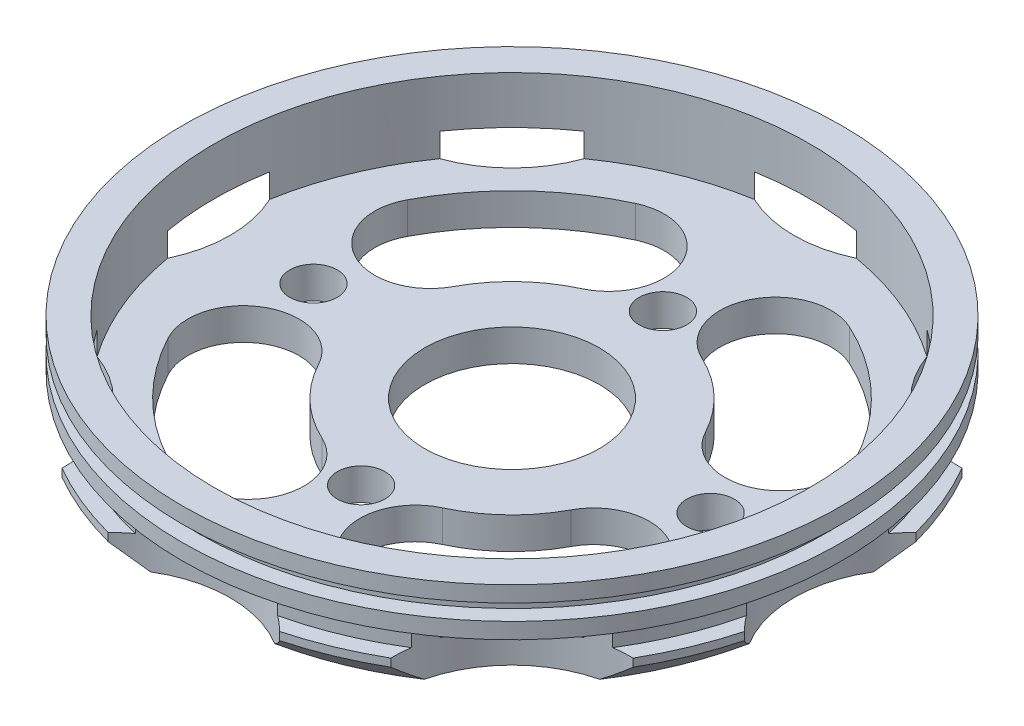
SolidWorks part; units mm, degrees
material "Gray Cast Iron"
ref_plane "Front Plane" through (0, 0, 0) normal (0, 0, 1) x (1, 0, 0)
ref_plane "Top Plane" through (0, 0, 0) normal (0, 1, 0) x (1, 0, 0)
ref_plane "Right Plane" through (0, 0, 0) normal (1, 0, 0) x (0, 0, -1)
sketch "Sketch1" plane through (0, 0, 0) normal (0, 1, 0) x (1, 0, 0)
  circle A0 centre (0, 0) radius 20.75
extrude "Boss-Extrude1" add sketch "Sketch1" along normal blind 6.5
ref_plane "Plane1" through (0, 5.5, 0) normal (0, 1, 0) x (1, 0, 0)
sketch "Sketch2" plane through (0, 5.5, 0) normal (0, 1, 0) x (1, 0, 0)
  circle A0 centre (0, 0) radius 20.75
  circle A1 centre (0, 0) radius 19.75
extrude "Cut-Extrude1" cut sketch "Sketch2" against normal blind 1
ref_plane "Plane2" through (0, 3.5, 0) normal (0, 1, 0) x (1, 0, 0)
sketch "Sketch3" plane through (0, 3.5, 0) normal (0, 1, 0) x (1, 0, 0)
  circle A0 centre (0, 0) radius 20.75
  circle A1 centre (0, 0) radius 19.75
  dimension "D1" = 1
extrude "Cut-Extrude2" cut sketch "Sketch3" against normal blind 1.5
chamfer "Chamfer1" distance 1.5 angle 45 1 edges at (0, 0, 20.75)
sketch "Sketch4" plane through (0, 6.5, 0) normal (0, 1, 0) x (1, 0, 0)
  circle A1 centre (0, 0) radius 18.75
extrude "Cut-Extrude3" cut sketch "Sketch4" against normal blind 4.5
sketch "Sketch5" plane through (0, 0, 0) normal (0, -1, 0) x (1, 0, 0)
  arc A1 (6, -20.75) -> (-6, -20.75) centre (0, -25.2522) ccw
  arc A2 (6, -20.75) -> (-6, -20.75) centre (0, -14.75) cw
  point P5 (6, -20.75)
  point P6 (0, -20.75)
  point P7 (-6, -20.75)
  point P8 (0, -17.75)
extrude "Cut-Extrude4" cut sketch "Sketch5" against normal blind 3.5
ref_axis "Axis1" through (0, 6.5, 0) along (0, -1, 0)
pattern_circular "CirPattern1" count 8 over 360 about axis through (0, 6.5, 0) along (0, -1, 0) of "Cut-Extrude4"
sketch "Sketch6" plane through (0, 0, 0) normal (0, -1, 0) x (-1, 0, 0)
  circle A0 centre (0, 9.5) radius 1.5
  circle A1 centre (-12.5, 0) radius 1.5
  circle A2 centre (12.5, 0) radius 1.5
  circle A3 centre (0, -9.5) radius 1.5
  arc A4 (-3.7862, 8.1649) -> (-7.9411, 4.2354) centre (0, 0) ccw
  arc A5 (-6.7309, 14.5153) -> (-14.1176, 7.5295) centre (0, 0) ccw
  arc A6 (14.1176, 7.5295) -> (7.9411, 4.2354) centre (11.0294, 5.8824) cw
  arc A7 (-1.9062, 12.3538) -> (-1.9085, 12.3535) centre (0, 0) ccw
  arc A8 (3.7862, 8.1649) -> (6.7309, 14.5153) centre (5.2585, 11.3401) cw
  arc A9 (1.9062, 12.3538) -> (1.9085, 12.3535) centre (0, 0) cw
  arc A10 (6.7309, 14.5153) -> (14.1176, 7.5295) centre (0, 0) cw
  arc A11 (-1.9062, 12.3538) -> (-1.9062, -12.3538) centre (0, 0) ccw construction
  arc A12 (-3.7862, 8.1649) -> (-6.7309, 14.5153) centre (-5.2585, 11.3401) ccw
  arc A13 (3.7862, 8.1649) -> (7.9411, 4.2354) centre (0, 0) cw
  arc A14 (-14.1176, 7.5295) -> (-7.9411, 4.2354) centre (-11.0294, 5.8824) ccw
  arc A15 (-12.2279, 2.594) -> (-12.41, 1.4973) centre (0, 0) ccw
  arc A16 (3.7862, -8.1649) -> (6.7309, -14.5153) centre (5.2585, -11.3401) ccw
  arc A17 (-1.3725, 8.8947) -> (-1.3725, -8.8947) centre (0, 0) ccw construction
  arc A18 (-3.7862, -8.1649) -> (-6.7309, -14.5153) centre (-5.2585, -11.3401) cw
  arc A19 (-14.1176, -7.5295) -> (-7.9411, -4.2354) centre (-11.0294, -5.8824) cw
  arc A20 (3.7862, -8.1649) -> (7.9411, -4.2354) centre (0, 0) ccw
  arc A21 (6.7309, -14.5153) -> (14.1176, -7.5295) centre (0, 0) ccw
  arc A22 (1.9062, -12.3538) -> (1.9085, -12.3535) centre (0, 0) ccw
  arc A23 (-1.9062, -12.3538) -> (-1.9085, -12.3535) centre (0, 0) cw
  arc A24 (14.1176, -7.5295) -> (7.9411, -4.2354) centre (11.0294, -5.8824) ccw
  arc A25 (-6.7309, -14.5153) -> (-14.1176, -7.5295) centre (0, 0) cw
  arc A26 (-3.7862, -8.1649) -> (-7.9411, -4.2354) centre (0, 0) cw
  circle A27 centre (0, 0) radius 5.5
  point P18 (0, 0)
  dimension "D1" = 9.5
  dimension "D5" = 3.5
  dimension "D2" = 9.5
  dimension "D3" = 12.5
  dimension "D4" = 12.5
extrude "Cut-Extrude5" cut sketch "Sketch6" against normal blind 3.5 contours A27 | A8 A13 A6 A10 | A0 | A5 A14 A4 A12 | A1 | A18 A26 A19 A25 | A21 A24 A20 A16 | A2 | A3 region at (0, 0, -9.5) region at (12.5, 0, 0) region at (8.3202, 0, -8.7977) region at (-12.5, 0, 0) region at (0, 0, 9.5) region at (-8.3202, 0, -8.7977) region at (-8.3202, 0, 8.7977) region at (8.3202, 0, 8.7977) region at (0, 0, 0)
